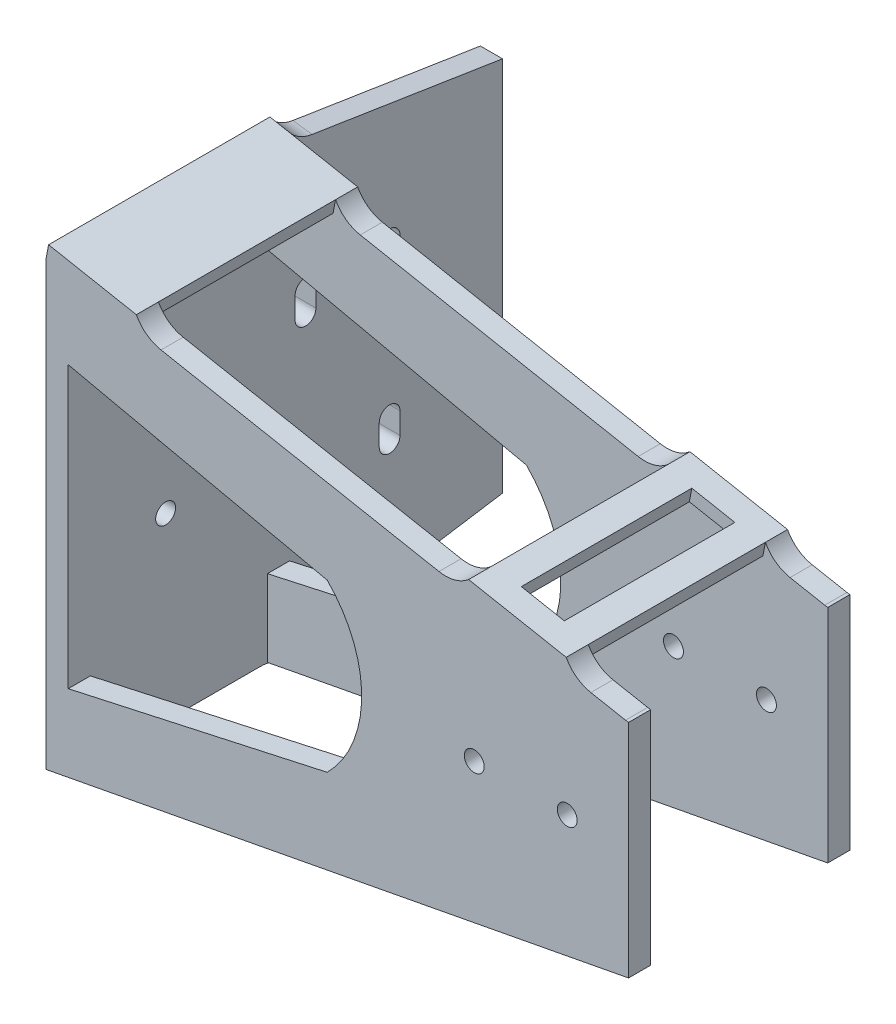
SolidWorks part; units mm, degrees
ref_plane "Front Plane" through (0, 0, 0) normal (0, 0, 1) x (1, 0, 0)
ref_plane "Top Plane" through (0, 0, 0) normal (0, 1, 0) x (1, 0, 0)
ref_plane "Right Plane" through (0, 0, 0) normal (1, 0, 0) x (0, 0, -1)
sketch "Sketch1" plane through (0, 0, 0) normal (0, 0, 1) x (1, 0, 0)
  line L2 (-51.15, -25) -> (-51.15, 25)
  line L12 (-51.15, 25) -> (-51.15, -25)
  line L14 (80.421, 25) -> (80.421, -25)
  line L23 (-51.15, -42.4887) -> (-51.15, 42.4887)
  line L24 (-51.15, 42.4887) -> (80.421, 25)
  line L25 (-51.15, -42.4887) -> (80.421, -25)
  line L28 (12.3488, 18.7973) -> (-46.15, 31.6848)
  line L30 (-46.15, -31.6848) -> (-46.15, 31.6848)
  line L35 (-46.15, -31.6848) -> (12.3488, -18.7973)
  circle A0 centre (45.5702, 0) radius 2.25
  circle A1 centre (66.5702, 0) radius 2.25
  arc A2 (12.3488, -18.7973) -> (12.3488, 18.7973) centre (-6.4484, 0) ccw
  point P0 (0, 0)
  point P8 (0, 0)
  point P9 (-42.5204, 0)
  point P23 (-51.15, 0)
  point P35 (51.15, -25)
  dimension "D5" = 4.5
  dimension "D6" = 4.5
  dimension "D1" = 102.3
  dimension "D2" = 50
  dimension "D8" = 21
extrude "Boss-Extrude1" add sketch "Sketch1" along normal blind 98.1 contours A0 A1 | A1 A0 | L2 | L2 region at (23.16, 0, 0)
sketch "Sketch10" plane through (-51.15, 0, 0) normal (-1, 0, 0) x (0, 0, 1)
  line L0 (0, -42.4887) -> (0, 42.4887) construction
  line L3 (98.1, -42.4887) -> (98.1, 42.4887) construction
  line L7 (25.5, 14.8) -> (25.5, 19.6) construction
  line L14 (25.5, -19.6) -> (25.5, -14.8) construction
  line L32 (23.15, 14.8) -> (23.15, 19.6)
  line L35 (27.85, 14.8) -> (27.85, 19.6)
  line L36 (44.5, 14.8) -> (44.5, 19.6) construction
  line L37 (42.15, 14.8) -> (42.15, 19.6)
  line L38 (46.85, 14.8) -> (46.85, 19.6)
  line L39 (44.5, -19.6) -> (44.5, -14.8) construction
  line L40 (42.15, -19.6) -> (42.15, -14.8)
  line L41 (46.85, -19.6) -> (46.85, -14.8)
  line L42 (23.1523, -19.6) -> (23.1523, -14.8)
  line L43 (27.8477, -19.6) -> (27.8477, -14.8)
  circle A0 centre (76.1, 8.3) radius 2.25
  circle A1 centre (76.1, -8.4) radius 2.25
  arc A18 (23.15, 14.8) -> (27.85, 14.8) centre (25.5, 14.8) ccw
  arc A19 (27.85, 19.6) -> (23.15, 19.6) centre (25.5, 19.6) ccw
  arc A20 (42.15, 14.8) -> (46.85, 14.8) centre (44.5, 14.8) ccw
  arc A21 (46.85, 19.6) -> (42.15, 19.6) centre (44.5, 19.6) ccw
  arc A22 (42.15, -19.6) -> (46.85, -19.6) centre (44.5, -19.6) ccw
  arc A23 (46.85, -14.8) -> (42.15, -14.8) centre (44.5, -14.8) ccw
  arc A24 (23.1523, -19.6) -> (27.8477, -19.6) centre (25.5, -19.6) ccw
  arc A25 (27.8477, -14.8) -> (23.1523, -14.8) centre (25.5, -14.8) ccw
  point P22 (25.5, 17.2)
  point P28 (44.5, 17.2)
  point P36 (44.5, -17.2)
  point P43 (25.5, -17.2)
  dimension "D1" = 4.5
  dimension "D2" = 4.5
  dimension "D4" = 19
  dimension "D5" = 22
  dimension "D6" = 22
  dimension "D7" = 19
  dimension "D8" = 25.5
  dimension "D9" = 25.5
  dimension "D11" = 4.8
  dimension "D12" = 4.8
  dimension "D13" = 4.8
  dimension "D14" = 4.8
  dimension "D15" = 4.7
  dimension "D16" = 4.7
  dimension "D17" = 4.6954
  dimension "D18" = 4.7
extrude "Cut-Extrude1" cut sketch "Sketch10" against normal through all both and the other way through all
sketch "Sketch13" plane through (0, 0, 0) normal (0, 1, 0) x (1, 0, 0)
  line L0 (-51.15, -98.1) -> (80.421, -98.1) construction
  line L1 (-51.15, 0) -> (-46.15, 0)
  line L2 (-51.15, 0) -> (-51.15, -98.1)
  line L3 (-51.15, -98.1) -> (-46.15, -98.1)
  line L4 (-46.15, 0) -> (-46.15, -98.1)
  line L5 (80.421, -98.1) -> (80.421, 0) construction
  line L6 (-46.15, -93.1) -> (80.421, -93.1)
  line L7 (-46.15, -93.1) -> (-46.15, -53.1)
  line L8 (-46.15, -53.1) -> (80.421, -53.1)
  line L9 (80.421, -93.1) -> (80.421, -53.1)
  line L12 (80.421, -48.1) -> (-46.15, -48.1)
  line L13 (80.421, -48.1) -> (80.421, 0)
  line L14 (80.421, 0) -> (-46.15, 0)
  line L15 (-46.15, -48.1) -> (-46.15, 0)
  dimension "D1" = 5
  dimension "D2" = 40
  dimension "D3" = 5
  dimension "D4" = 5
extrude "Cut-Extrude3" cut sketch "Sketch13" against normal through all both and the other way through all contours L13 L14 L4 L12 | L6 L9 L8 L4 | L13 L12 L15 L14 | L7 L6 L9 L8 region at (17.1355, 0, 24.05) region at (17.1355, 0, 73.1)
sketch "Sketch15" plane through (0, 0, 98.1) normal (0, 0, 1) x (1, 0, 0)
  line L1 (-51.15, -49.9941) -> (-51.15, -42.4887)
  line L2 (-51.15, 49.9941) -> (79.7367, 25.091)
  line L3 (-51.15, 42.4887) -> (80.421, 25) construction
  line L4 (79.7367, 25.091) -> (80.421, -25)
  line L5 (80.421, -25) -> (-51.15, -49.9941)
  line L6 (79.7367, 25.091) -> (-51.15, 42.4887)
  line L7 (-51.15, -42.4887) -> (80.421, -25)
  line L8 (-51.15, 42.4887) -> (-51.15, 49.9941)
  point P3 (-51.15, 0)
  line M12 (-51.15, -42.4887) -> (80.421, -25)
  line M14 (80.421, 25) -> (-51.15, 42.4887)
extrude "Boss-Extrude2" add sketch "Sketch15" against normal blind 50 contours L8 L2 M14 | L5 L1 M12 region at (-7.5211, 39.1913, 98.1) region at (-7.293, -39.161, 98.1)
sketch "Sketch16" plane through (0, 0, 0) normal (0, 1, 0) x (1, 0, 0)
  line L0 (-51.15, -48.1) -> (79.7367, -48.1) construction
  line L9 (-46.15, -53.1) -> (82.445, -53.1)
  line L10 (-46.15, -53.1) -> (-46.15, -93.1)
  line L11 (-46.15, -93.1) -> (82.445, -93.1)
  line L12 (82.445, -53.1) -> (82.445, -93.1)
  dimension "D1" = 5
extrude "Cut-Extrude4" cut sketch "Sketch16" against normal through all both and the other way through all
sketch "Sketch17" plane through (-51.15, 0, 0) normal (-1, 0, 0) x (0, 0, 1)
  line L9 (51.8038, -33.7915) -> (48.1, -49.9941)
  line L11 (48.1, 49.9941) -> (53.4022, 34.2733)
  line L14 (53.4022, 34.2733) -> (13.0944, 25.7226)
  line L15 (13.0944, 25.7226) -> (14.934, -26.8058)
  line L16 (14.934, -26.8058) -> (51.8038, -33.7915)
  line L18 (0, -42.4887) -> (0, 42.4887)
  line L20 (0, 42.4887) -> (48.1, 49.9941)
  line L21 (48.1, 42.4887) -> (48.1, 49.9941) construction
  line L22 (0, -42.4887) -> (48.1, -49.9941)
  line L23 (48.1, -49.9941) -> (48.1, -42.4887) construction
extrude "Boss-Extrude6" add sketch "Sketch17" against normal blind 5
fillet "Fillet3" radius 8 1 edges at (-48.65, 49.5185, 48.2604)
fillet "Fillet4" radius 8 1 edges at (-48.65, -49.5192, 48.2086)
sketch "Sketch19" plane through (7.3928, 38.8555, 0) normal (0.1869, 0.9824, 0) x (0.9824, -0.1869, 0)
  line L0 (36.991, -98.1) -> (36.991, -48.1)
  line L1 (-59.5931, -98.1) -> (73.6417, -98.1) construction
  line L2 (-54.5034, -48.1) -> (73.6417, -48.1) construction
  line L3 (59.4262, -98.1) -> (59.4262, -48.1)
sketch "Sketch20" plane through (7.3928, 38.8555, 0) normal (0.1869, 0.9824, 0) x (0.9824, -0.1869, 0)
  line L1 (59.4262, -48.1) -> (36.991, -48.1)
  line L2 (59.4262, -48.1) -> (59.4262, -98.1)
  line L3 (59.4262, -98.1) -> (36.991, -98.1)
  line L4 (36.991, -48.1) -> (36.991, -98.1)
extrude "Boss-Extrude7" add sketch "Sketch20" along normal blind 3
fillet "Fillet5" radius 8 4 edges at (43.7319, 31.9414, 50.6) (43.7319, 31.9414, 95.6) (65.7718, 27.748, 95.6) (65.7718, 27.748, 50.6)
sketch "Sketch21" plane through (7.9536, 41.8026, 0) normal (0.1869, 0.9824, 0) x (0.9824, -0.1869, 0)
  line L5 (43.2668, -92.3568) -> (53.1504, -92.3568)
  line L6 (43.2668, -92.3568) -> (43.2668, -53.8432)
  line L7 (43.2668, -53.8432) -> (53.1504, -53.8432)
  line L8 (53.1504, -92.3568) -> (53.1504, -53.8432)
extrude "Cut-Extrude5" cut sketch "Sketch21" against normal through all both and the other way through all contours L6 L5 L8 L7
sketch "Sketch22" plane through (7.3928, 38.8555, 0) normal (0.1869, 0.9824, 0) x (0.9824, -0.1869, 0)
  line L1 (-39.4144, -48.1) -> (-59.5931, -48.1)
  line L2 (-39.4144, -48.1) -> (-39.4144, -98.1)
  line L3 (-39.4144, -98.1) -> (-59.5931, -98.1)
  line L4 (-59.5931, -48.1) -> (-59.5931, -98.1)
extrude "Boss-Extrude8" add sketch "Sketch22" along normal blind 3
fillet "Fillet6" radius 8 2 edges at (-31.327, 46.2225, 95.6) (-31.327, 46.2225, 50.6)
fillet "Fillet7" radius 8 1 edges at (-48.65, 49.9941, 48.1)
